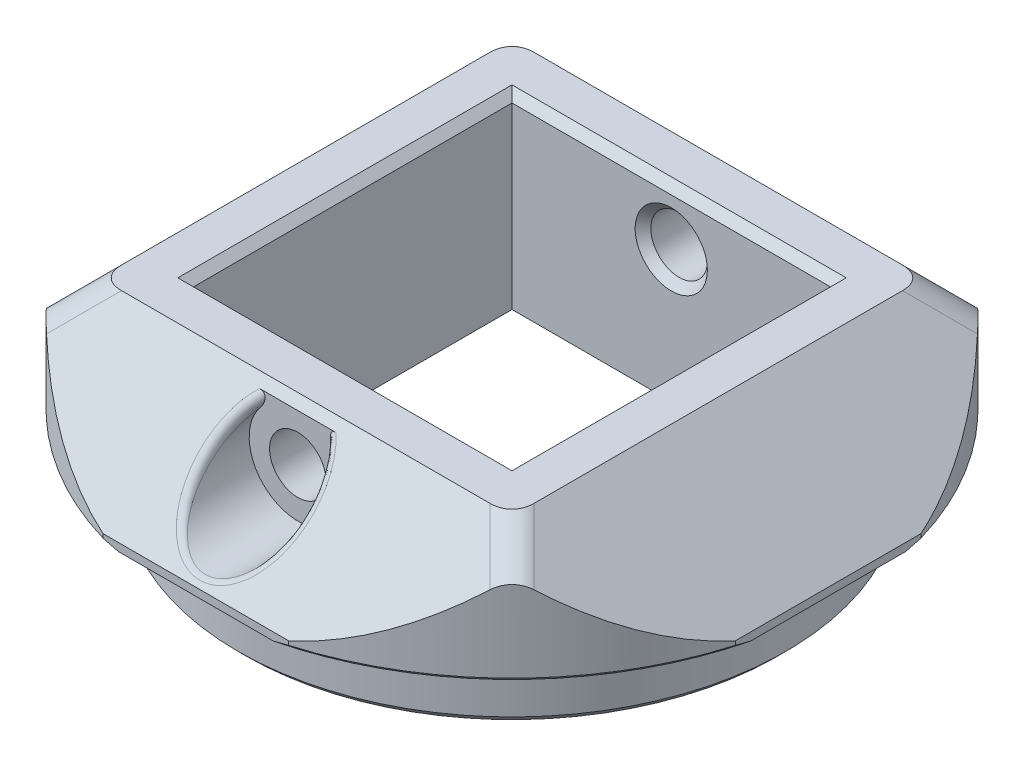
SolidWorks part; units mm, degrees
note: The reader was unsure of these and kept them because the rebuilt part matched: shared geometry of "Sketch8<3>".
ref_plane "Front Plane" through (0, 0, 0) normal (0, 0, 1) x (1, 0, 0)
ref_plane "Top Plane" through (0, 0, 0) normal (0, 1, 0) x (1, 0, 0)
ref_plane "Right Plane" through (0, 0, 0) normal (1, 0, 0) x (0, 0, -1)
sketch "Sketch1" plane through (0, 0, 0) normal (0, 1, 0) x (1, 0, 0)
  line L1 (-10.15, -10.15) -> (10.15, -10.15)
  line L2 (-10.15, -10.15) -> (-10.15, 10.15)
  line L3 (-10.15, 10.15) -> (10.15, 10.15)
  line L4 (10.15, -10.15) -> (10.15, 10.15)
  line L5 (-10.15, -10.15) -> (10.15, 10.15) construction
  line L6 (-10.15, 10.15) -> (10.15, -10.15) construction
  circle A0 centre (0, 0) radius 17.45
  point P0 (0, 0)
  point P5 (0, 0)
  dimension "D2" = 34.9
  dimension "D1" = 20.3
extrude "Boss-Extrude1" add sketch "Sketch1" along normal blind 4.9
sketch "Sketch7" plane through (0, 4.9, 0) normal (0, 1, 0) x (1, 0, 0)
  line L1 (-10.15, 10.15) -> (10.15, 10.15)
  line L2 (-10.15, 10.15) -> (-10.15, -10.15)
  line L3 (-10.15, -10.15) -> (10.15, -10.15)
  line L4 (10.15, 10.15) -> (10.15, -10.15)
  circle A0 centre (0, 0) radius 21
  dimension "D1" = 42
extrude "Boss-Extrude5" add sketch "Sketch7" along normal blind 0.5
sketch "Sketch6" plane through (0, 5.4, 0) normal (0, 1, 0) x (1, 0, 0)
  line L1 (-10.15, 10.15) -> (10.15, 10.15)
  line L2 (-10.15, 10.15) -> (-10.15, -10.15)
  line L3 (-10.15, -10.15) -> (10.15, -10.15)
  line L4 (10.15, 10.15) -> (10.15, -10.15)
  line L5 (-13.15, -13.15) -> (13.15, -13.15)
  line L6 (-13.15, -13.15) -> (-13.15, 13.15)
  line L7 (-13.15, 13.15) -> (13.15, 13.15)
  line L8 (13.15, -13.15) -> (13.15, 13.15)
  line L9 (-13.15, -13.15) -> (13.15, 13.15) construction
  line L10 (-13.15, 13.15) -> (13.15, -13.15) construction
  point P4 (0, 0)
  dimension "D1" = 3
extrude "Boss-Extrude4" add sketch "Sketch6" along normal blind 7
chamfer "Chamfer1" distance 7 angle 45 4 edges at (-13.15, 5.4, 0) (0, 5.4, -13.15) (13.15, 5.4, 0) (0, 5.4, 13.15)
sketch "Sketch8" plane through (0, 0, -10.15) normal (0, 0, 1) x (1, 0, 0)
  line L0 (0, 12.4) -> (0, 5.4) construction
  line L1 (-13.15, 12.4) -> (13.15, 12.4) construction
  line L2 (5.9142, 5.4) -> (-5.9142, 5.4) construction
  circle A0 centre (0, 8.9) radius 1.8
  circle A1 centre (0, 8.9) radius 3.1
  dimension "D1" = 3.6
  dimension "D2" = 6.2
extrude "Cut-Extrude5" cut sketch "Sketch8" against normal through all contours A0 L0 | L0 A0
extrude "Cut-Extrude6" cut sketch "Sketch8<3>" against normal through all from offset 3.5 offset against normal yes
sketch "Sketch8<3>" plane through (0, 0, -10.15) normal (0, 0, 1) x (1, 0, 0) same geometry as "Sketch8"
mirror "Mirror1" about plane through (0, 0, 0) normal (0, 0, 1) of "Cut-Extrude6", "Cut-Extrude5"
sketch "Sketch9" plane through (0, 5.4, 0) normal (0, 1, 0) x (1, 0, 0)
  line L0 (-5.9142, 20.15) -> (5.9142, 20.15)
  line L1 (5.9142, 20.15) -> (20.15, 20.15)
  line L2 (20.15, 20.15) -> (20.15, 5.9142)
  line L3 (20.15, 5.9142) -> (20.15, -5.9142)
  line L4 (20.15, -5.9142) -> (20.15, -20.15)
  line L5 (20.15, -20.15) -> (5.9142, -20.15)
  line L6 (5.9142, -20.15) -> (-5.9142, -20.15)
  line L7 (-5.9142, -20.15) -> (-20.15, -20.15)
  line L8 (-20.15, -20.15) -> (-20.15, -5.9142)
  line L9 (-20.15, -5.9142) -> (-20.15, 5.9142)
  line L10 (-20.15, 5.9142) -> (-20.15, 20.15)
  line L11 (-20.15, 20.15) -> (-5.9142, 20.15)
  line L13 (-26.7487, 26.8068) -> (29.3423, 26.8068)
  line L14 (-26.7487, 26.8068) -> (-26.7487, -29.5939)
  line L15 (-26.7487, -29.5939) -> (29.3423, -29.5939)
  line L16 (29.3423, 26.8068) -> (29.3423, -29.5939)
extrude "Cut-Extrude7" cut sketch "Sketch9" against normal through all
sketch "Sketch10" plane through (0, 0, 0) normal (0, -1, 0) x (1, 0, 0)
  line L0 (10.15, 0) -> (17.45, 0) construction
  line L2 (0, 0) -> (10.15, 0) construction
  line L3 (10.15, 10.15) -> (10.15, -10.15) construction
  line L4 (0, 0) -> (0, 10.15) construction
  line L5 (-10.15, 10.15) -> (10.15, 10.15) construction
  circle A0 centre (0, 0) radius 17.45 construction
  circle A1 centre (13.8, 0) radius 2.2
  circle A3 centre (-13.8, 0) radius 2.2
  dimension "D1" = 4.4
extrude "Cut-Extrude8" cut sketch "Sketch10" against normal blind 7
chamfer "Chamfer2" distance 0.5 angle 45 13 edges at (0, 12.4, 10.15) (10.15, 12.4, 0) (0, 12.4, -10.15) (-10.15, 12.4, 0) (0, 0, 10.15) (-10.15, 0, 0) (0, 0, -10.15) (10.15, 0, 0) (0, 0, 17.45) (13.8, 0, -2.2) (-13.8, 0, 2.2) (1.8, 8.9, -10.15) (1.8, 8.9, 10.15)
chamfer "Chamfer3" distance 0.25 angle 45 4 edges at (-14.8492, 4.9, 14.8492) (14.8492, 4.9, 14.8492) (14.8492, 4.9, -14.8492) (-14.8492, 4.9, -14.8492)
fillet "Fillet1" radius 0.5 2 edges at (0, 5.8, 19.75) (0, 5.8, -19.75)
fillet "Fillet2" radius 2 4 edges at (-13.9996, 11.5504, -13.9996) (-13.9996, 11.5504, 13.9996) (13.9996, 11.5504, 13.9996) (13.9996, 11.5504, -13.9996)
ref_plane "Plane1" through (0, 0, 0) normal (-0.7071, 0, 0.7071) x (0.7071, 0, 0.7071)
